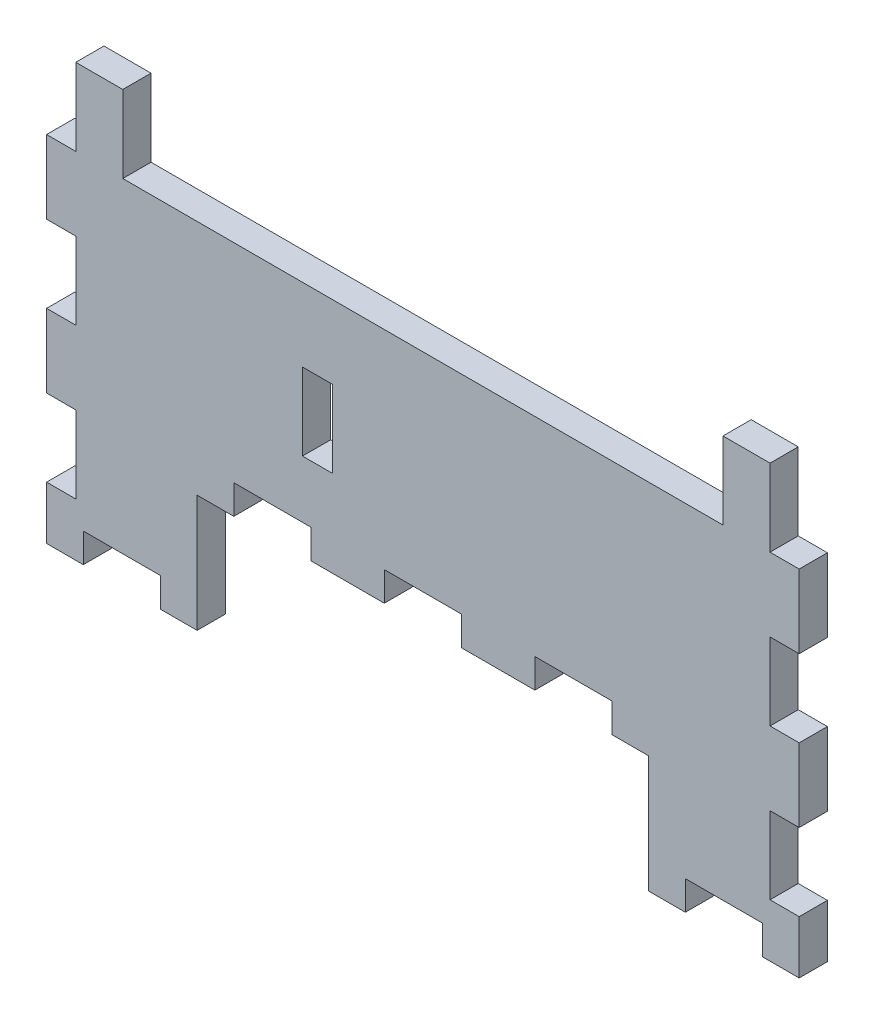
SolidWorks part; units mm, degrees
ref_plane "Front Plane" through (0, 0, 0) normal (0, 0, 1) x (1, 0, 0)
ref_plane "Top Plane" through (0, 0, 0) normal (0, 1, 0) x (1, 0, 0)
ref_plane "Right Plane" through (0, 0, 0) normal (1, 0, 0) x (0, 0, -1)
sketch "Sketch1" plane through (0, 0, 0) normal (0, 0, 1) x (1, 0, 0)
  line L0 (0, 52.125) -> (11.2, 52.125)
  line L1 (80, 52.125) -> (80, 3.175)
  line L2 (80, 3.175) -> (64, 3.175)
  line L3 (64, 3.175) -> (64, 15.625)
  line L4 (64, 15.625) -> (16, 15.625)
  line L5 (16, 15.625) -> (16, 3.175)
  line L6 (16, 3.175) -> (0, 3.175)
  line L7 (0, 3.175) -> (0, 52.125)
  line L8 (16, 3.175) -> (0, 3.175) construction
  line L9 (0, 15.625) -> (80, 15.625) construction
  line L10 (16, 18.625) -> (16, 3.175) construction
  line L11 (64, 18.625) -> (64, 3.175) construction
  line L12 (80, 3.175) -> (80, 52.125) construction
  line L13 (0, 3.175) -> (0, 52.125) construction
  line L15 (40, 15.625) -> (40, 52.125) construction
  line L16 (40, 0) -> (40, 67.125) construction
  line L17 (3, 49.125) -> (3, 6.175) construction
  line L18 (3, 6.175) -> (16, 6.175) construction
  line L19 (64, 6.175) -> (77, 6.175) construction
  line L20 (77, 6.175) -> (77, 49.125) construction
  line L21 (77, 49.125) -> (3, 49.125) construction
  line L22 (0, 18.625) -> (80, 18.625) construction
  line L23 (64, 15.625) -> (80, 15.625) construction
  line L24 (16, 15.625) -> (0, 15.625) construction
  line L25 (8, 3.175) -> (8, 6.175) construction
  line L26 (72, 3.175) -> (72, 6.175) construction
  line L27 (77, 6.175) -> (77, 49.125) construction
  line L28 (77, 6.175) -> (64, 6.175) construction
  line L29 (72, 3.175) -> (72, 6.175) construction
  line L30 (16, 6.175) -> (3, 6.175) construction
  line L31 (3, 6.175) -> (3, 49.125) construction
  line L32 (8, 3.175) -> (8, 6.175) construction
  line L33 (80, 18.625) -> (0, 18.625) construction
  line L34 (77, 49.125) -> (3, 49.125) construction
  line L35 (45.3, 50.175) -> (45.3, 8.175) construction
  line L36 (45.3, 8.175) -> (42.3, 8.175) construction
  line L37 (42.3, 50.175) -> (42.3, 8.175) construction
  line L38 (45.3, 50.175) -> (42.3, 50.175) construction
  line L39 (45.3, 50.175) -> (45.3, 8.175) construction
  line L40 (45.3, 8.175) -> (42.3, 8.175) construction
  line L41 (42.3, 50.175) -> (42.3, 8.175) construction
  line L42 (45.3, 50.175) -> (42.3, 50.175) construction
  line L43 (71.8, 40.925) -> (71.8, 52.125) construction
  line L44 (0, 52.125) -> (80, 52.125) construction
  line L45 (8.2, 52.125) -> (8.2, 40.925) construction
  line L46 (8.2, 40.925) -> (71.8, 40.925) construction
  line L47 (71.8, 52.125) -> (71.8, 40.925) construction
  line L48 (8.2, 40.925) -> (8.2, 52.125) construction
  line L49 (16.5, 40.925) -> (8.2, 40.925) construction
  line L50 (8.2, 52.125) -> (16.5, 52.125) construction
  line L51 (11.2, 49.125) -> (11.2, 43.925) construction
  line L53 (11.2, 52.125) -> (11.2, 43.925)
  line L54 (11.2, 43.925) -> (68.8, 43.925) construction
  line L55 (68.8, 52.125) -> (68.8, 43.925)
  line L56 (68.8, 52.125) -> (80, 52.125)
  line L57 (68.8, 49.125) -> (68.8, 43.925) construction
  line L59 (68.8, 43.925) -> (63.5, 43.925) construction
  line L60 (16.5, 52.125) -> (16.5, 49.125) construction
  line L61 (16.5, 43.925) -> (16.5, 40.925)
  line L62 (16.5, 52.125) -> (16.5, 49.125) construction
  line L63 (63.5, 52.125) -> (63.5, 49.125) construction
  line L64 (63.5, 43.925) -> (63.5, 40.925)
  line L65 (63.5, 52.125) -> (63.5, 49.125) construction
  line L66 (48.3, 53.175) -> (48.3, 5.175) construction
  line L67 (48.3, 5.175) -> (39.3, 5.175) construction
  line L70 (39.3, 53.175) -> (39.3, 5.175) construction
  line L71 (48.3, 53.175) -> (39.3, 53.175) construction
  line L72 (63.5, 43.925) -> (68.8, 43.925)
  line L73 (11.2, 43.925) -> (16.5, 43.925)
  line L74 (39.3, 53.175) -> (39.3, 44.225) construction
  line L80 (16.5, 40.925) -> (63.5, 40.925)
sketch "Sketch2" plane through (0, 0, 0) normal (1, 0, 0) x (0, 0, -1)
  line L1 (0, 52.125) -> (3, 52.125)
  line L2 (0, 52.125) -> (0, 3.175)
  line L3 (0, 3.175) -> (3, 3.175)
  line L4 (3, 52.125) -> (3, 3.175)
extrude "Boss-Extrude1" add sketch "Sketch1" against normal up to vertex (3 mm away) up to point (0, 52.125, -3)
sketch "Sketch3" plane through (0, 0, 0) normal (0, 0, 1) x (1, 0, 0)
  line L7 (44, 18.625) -> (36, 18.625)
  line L8 (44, 15.625) -> (44, 18.625)
  line L9 (36, 15.625) -> (44, 15.625)
  line L10 (36, 18.625) -> (36, 15.625)
  line L11 (44, 18.625) -> (36, 18.625) construction
  line L20 (44, 15.625) -> (44, 18.625) construction
  line L21 (36, 15.625) -> (44, 15.625) construction
  line L22 (36, 18.625) -> (36, 15.625) construction
  line L23 (60, 15.625) -> (60, 18.625)
  line L24 (52, 15.625) -> (60, 15.625)
  line L25 (52, 18.625) -> (52, 15.625)
  line L26 (60, 18.625) -> (52, 18.625)
  line L27 (60, 15.625) -> (60, 18.625) construction
  line L34 (52, 15.625) -> (60, 15.625) construction
  line L35 (52, 18.625) -> (52, 15.625) construction
  line L36 (60, 18.625) -> (52, 18.625) construction
  line L37 (28, 18.625) -> (20, 18.625)
  line L38 (28, 15.625) -> (28, 18.625)
  line L39 (20, 15.625) -> (28, 15.625)
  line L40 (20, 18.625) -> (20, 15.625)
  line L41 (28, 18.625) -> (20, 18.625) construction
  line L42 (28, 15.625) -> (28, 18.625) construction
  line L43 (20, 15.625) -> (28, 15.625) construction
  line L44 (20, 18.625) -> (20, 15.625) construction
  line L45 (80, 16.925) -> (77, 16.925)
  line L46 (80, 8.925) -> (80, 16.925)
  line L47 (77, 8.925) -> (80, 8.925)
  line L48 (77, 16.925) -> (77, 8.925)
  line L49 (80, 16.925) -> (77, 16.925) construction
  line L50 (80, 8.925) -> (80, 16.925) construction
  line L51 (3, 40.925) -> (3, 49.125)
  line L52 (3, 49.125) -> (8.2, 49.125)
  line L53 (8.2, 49.125) -> (8.2, 40.925)
  line L56 (8.2, 40.925) -> (16.5, 40.925)
  line L57 (16.5, 40.925) -> (16.5, 43.925)
  line L58 (16.5, 43.925) -> (11.2, 43.925)
  line L59 (11.2, 43.925) -> (11.2, 52.125)
  line L60 (11.2, 52.125) -> (0, 52.125)
  line L61 (0, 52.125) -> (0, 40.925)
  line L62 (0, 40.925) -> (3, 40.925)
  line L63 (3, 40.925) -> (3, 49.125) construction
  line L64 (3, 49.125) -> (8.2, 49.125) construction
  line L65 (8.2, 49.125) -> (8.2, 40.925) construction
  line L66 (8.2, 40.925) -> (16.5, 40.925) construction
  line L67 (16.5, 40.925) -> (16.5, 43.925) construction
  line L68 (16.5, 43.925) -> (11.2, 43.925) construction
  line L69 (11.2, 43.925) -> (11.2, 52.125) construction
  line L70 (11.2, 52.125) -> (0, 52.125) construction
  line L71 (0, 52.125) -> (0, 40.925) construction
  line L72 (0, 40.925) -> (3, 40.925) construction
  line L73 (77, 8.925) -> (80, 8.925) construction
  line L74 (77, 16.925) -> (77, 8.925) construction
  line L75 (30.3, 32.925) -> (27.3, 32.925)
  line L76 (30.3, 24.925) -> (30.3, 32.925)
  line L77 (27.3, 24.925) -> (30.3, 24.925)
  line L78 (27.3, 32.925) -> (27.3, 24.925)
  line L79 (30.3, 32.925) -> (27.3, 32.925) construction
  line L80 (30.3, 24.925) -> (30.3, 32.925) construction
  line L81 (27.3, 24.925) -> (30.3, 24.925) construction
  line L82 (27.3, 32.925) -> (27.3, 24.925) construction
  line L83 (12, 6.175) -> (4, 6.175)
  line L84 (12, 3.175) -> (12, 6.175)
  line L85 (4, 3.175) -> (12, 3.175)
  line L86 (4, 6.175) -> (4, 3.175)
  line L87 (12, 6.175) -> (4, 6.175) construction
  line L104 (12, 3.175) -> (12, 6.175) construction
  line L105 (4, 3.175) -> (12, 3.175) construction
  line L106 (4, 6.175) -> (4, 3.175) construction
  line L107 (0, 8.925) -> (3, 8.925)
  line L108 (0, 16.925) -> (0, 8.925)
  line L109 (3, 16.925) -> (0, 16.925)
  line L110 (3, 8.925) -> (3, 16.925)
  line L111 (0, 8.925) -> (3, 8.925) construction
  line L112 (0, 16.925) -> (0, 8.925) construction
  line L113 (3, 16.925) -> (0, 16.925) construction
  line L114 (3, 8.925) -> (3, 16.925) construction
  line L115 (0, 24.925) -> (3, 24.925)
  line L116 (0, 32.925) -> (0, 24.925)
  line L117 (3, 32.925) -> (0, 32.925)
  line L118 (3, 24.925) -> (3, 32.925)
  line L119 (0, 24.925) -> (3, 24.925) construction
  line L120 (0, 32.925) -> (0, 24.925) construction
  line L121 (3, 32.925) -> (0, 32.925) construction
  line L122 (3, 24.925) -> (3, 32.925) construction
  line L123 (80, 32.925) -> (77, 32.925)
  line L124 (80, 24.925) -> (80, 32.925)
  line L125 (77, 24.925) -> (80, 24.925)
  line L126 (77, 32.925) -> (77, 24.925)
  line L127 (80, 32.925) -> (77, 32.925) construction
  line L128 (80, 24.925) -> (80, 32.925) construction
  line L129 (77, 40.925) -> (80, 40.925)
  line L130 (80, 40.925) -> (80, 52.125)
  line L131 (80, 52.125) -> (68.8, 52.125)
  line L132 (68.8, 52.125) -> (68.8, 43.925)
  line L133 (68.8, 43.925) -> (63.5, 43.925)
  line L134 (63.5, 43.925) -> (63.5, 40.925)
  line L135 (63.5, 40.925) -> (71.8, 40.925)
  line L136 (71.8, 40.925) -> (71.8, 49.125)
  line L137 (71.8, 49.125) -> (77, 49.125)
  line L138 (77, 49.125) -> (77, 40.925)
  line L139 (77, 40.925) -> (80, 40.925) construction
  line L140 (80, 40.925) -> (80, 52.125) construction
  line L141 (80, 52.125) -> (68.8, 52.125) construction
  line L142 (68.8, 52.125) -> (68.8, 43.925) construction
  line L143 (68.8, 43.925) -> (63.5, 43.925) construction
  line L144 (63.5, 43.925) -> (63.5, 40.925) construction
  line L145 (63.5, 40.925) -> (71.8, 40.925) construction
  line L146 (71.8, 40.925) -> (71.8, 49.125) construction
  line L147 (71.8, 49.125) -> (77, 49.125) construction
  line L148 (77, 49.125) -> (77, 40.925) construction
  line L149 (77, 24.925) -> (80, 24.925) construction
  line L150 (77, 32.925) -> (77, 24.925) construction
  line L151 (68, 6.175) -> (68, 3.175)
  line L152 (68, 3.175) -> (76, 3.175)
  line L153 (76, 3.175) -> (76, 6.175)
  line L154 (76, 6.175) -> (68, 6.175)
  line L155 (68, 6.175) -> (68, 3.175) construction
  line L156 (68, 3.175) -> (76, 3.175) construction
  line L157 (76, 3.175) -> (76, 6.175) construction
  line L158 (76, 6.175) -> (68, 6.175) construction
  line L215 (44.1, 18.725) -> (35.9, 18.725)
  line L216 (35.9, 18.725) -> (35.9, 15.525)
  line L217 (35.9, 15.525) -> (44.1, 15.525)
  line L218 (44.1, 15.525) -> (44.1, 18.725)
  line L219 (60.1, 15.525) -> (60.1, 18.725)
  line L220 (60.1, 18.725) -> (51.9, 18.725)
  line L221 (51.9, 18.725) -> (51.9, 15.525)
  line L222 (51.9, 15.525) -> (60.1, 15.525)
  line L223 (28.1, 18.725) -> (19.9, 18.725)
  line L224 (19.9, 18.725) -> (19.9, 15.525)
  line L225 (19.9, 15.525) -> (28.1, 15.525)
  line L226 (28.1, 15.525) -> (28.1, 18.725)
  line L227 (80.1, 17.025) -> (76.9, 17.025)
  line L228 (76.9, 17.025) -> (76.9, 8.825)
  line L229 (76.9, 8.825) -> (80.1, 8.825)
  line L230 (80.1, 8.825) -> (80.1, 17.025)
  line L231 (3.1, 40.825) -> (3.1, 49.025)
  line L232 (3.1, 49.025) -> (8.1, 49.025)
  line L233 (8.1, 49.025) -> (8.1, 40.825)
  line L234 (8.1, 40.825) -> (71.9, 40.825)
  line L236 (68.7, 44.025) -> (11.3, 44.025)
  line L237 (11.3, 44.025) -> (11.3, 52.225)
  line L238 (11.3, 52.225) -> (-0.1, 52.225)
  line L239 (-0.1, 52.225) -> (-0.1, 40.825)
  line L240 (-0.1, 40.825) -> (3.1, 40.825)
  line L241 (30.4, 33.025) -> (27.2, 33.025)
  line L242 (27.2, 33.025) -> (27.2, 24.825)
  line L243 (27.2, 24.825) -> (30.4, 24.825)
  line L244 (30.4, 24.825) -> (30.4, 33.025)
  line L245 (12.1, 6.275) -> (3.9, 6.275)
  line L246 (3.9, 6.275) -> (3.9, 3.075)
  line L247 (3.9, 3.075) -> (12.1, 3.075)
  line L248 (12.1, 3.075) -> (12.1, 6.275)
  line L249 (-0.1, 8.825) -> (3.1, 8.825)
  line L250 (3.1, 8.825) -> (3.1, 17.025)
  line L251 (3.1, 17.025) -> (-0.1, 17.025)
  line L252 (-0.1, 17.025) -> (-0.1, 8.825)
  line L253 (-0.1, 24.825) -> (3.1, 24.825)
  line L254 (3.1, 24.825) -> (3.1, 33.025)
  line L255 (3.1, 33.025) -> (-0.1, 33.025)
  line L256 (-0.1, 33.025) -> (-0.1, 24.825)
  line L257 (80.1, 33.025) -> (76.9, 33.025)
  line L258 (76.9, 33.025) -> (76.9, 24.825)
  line L259 (76.9, 24.825) -> (80.1, 24.825)
  line L260 (80.1, 24.825) -> (80.1, 33.025)
  line L261 (76.9, 40.825) -> (80.1, 40.825)
  line L262 (80.1, 40.825) -> (80.1, 52.225)
  line L263 (80.1, 52.225) -> (68.7, 52.225)
  line L264 (68.7, 52.225) -> (68.7, 44.025)
  line L267 (8.1, 40.825) -> (16.6, 40.825) construction
  line L268 (71.9, 40.825) -> (71.9, 49.025)
  line L269 (71.9, 49.025) -> (76.9, 49.025)
  line L270 (76.9, 49.025) -> (76.9, 40.825)
  line L271 (67.9, 6.275) -> (67.9, 3.075)
  line L272 (67.9, 3.075) -> (76.1, 3.075)
  line L273 (76.1, 3.075) -> (76.1, 6.275)
  line L274 (76.1, 6.275) -> (67.9, 6.275)
  line L275 (16.6, 40.825) -> (16.6, 44.025) construction
  line L276 (63.4, 44.025) -> (63.4, 40.825) construction
  line L277 (68.7, 44.025) -> (63.4, 44.025) construction
  line L278 (63.4, 40.825) -> (71.9, 40.825) construction
  line L279 (16.6, 44.025) -> (11.3, 44.025) construction
  dimension "D1" = 0
  dimension "D2" = 0
  dimension "D3" = 0
  dimension "D4" = 0
  dimension "D5" = 0
  dimension "D6" = 0
  dimension "D7" = 0
  dimension "D8" = 0
  dimension "D9" = 0
  dimension "D10" = 0
  dimension "D11" = 0
  dimension "D12" = 0
  dimension "D13" = 0.1
extrude "Cut-Extrude3" cut sketch "Sketch3" against normal through all
